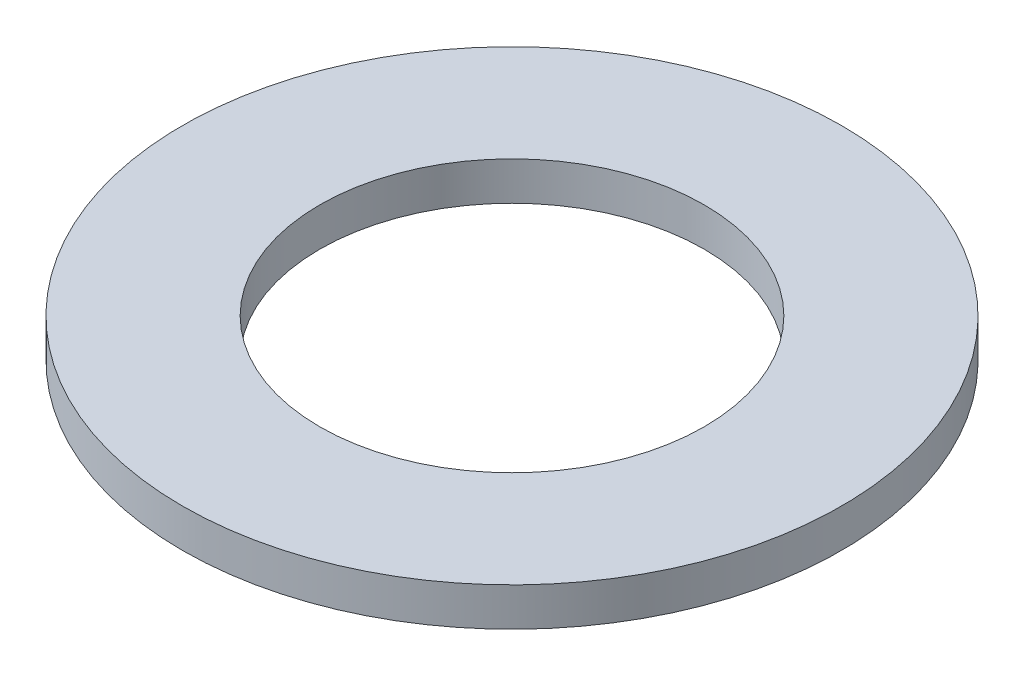
SolidWorks part; units mm, degrees
ref_plane "Front Plane" through (0, 0, 0) normal (0, 0, 1) x (1, 0, 0)
ref_plane "Top Plane" through (0, 0, 0) normal (0, 1, 0) x (1, 0, 0)
ref_plane "Right Plane" through (0, 0, 0) normal (1, 0, 0) x (0, 0, -1)
sketch "Sketch1" plane through (0, 0, 0) normal (0, 1, 0) x (1, 0, 0)
  circle A0 centre (0, 0) radius 60
  dimension "FLANGE_OD" = 120
extrude "Boss-Extrude1" add sketch "Sketch1" along normal blind 7
sketch "Sketch2" plane through (0, 0, 0) normal (0, 1, 0) x (1, 0, 0)
  circle A0 centre (0, 0) radius 35
  dimension "BORE_D" = 70
extrude "Cut-Extrude1" cut sketch "Sketch2" along normal through all
sketch "Sketch3" plane through (0, 7, 0) normal (0, 1, 0) x (1, 0, 0)
  circle A0 centre (0, 0) radius 25.6822 construction
  circle A1 centre (-25.6822, 0) radius 4.0207
  dimension "BOLT_D" = 8.0414
  dimension "BOLT_PCD" = 51.3643
extrude "Cut-Extrude2" cut sketch "Sketch3" against normal blind 5.9142 rebuild error yes
pattern_circular "CirPattern1" count 6 over 360 rebuild error yes
